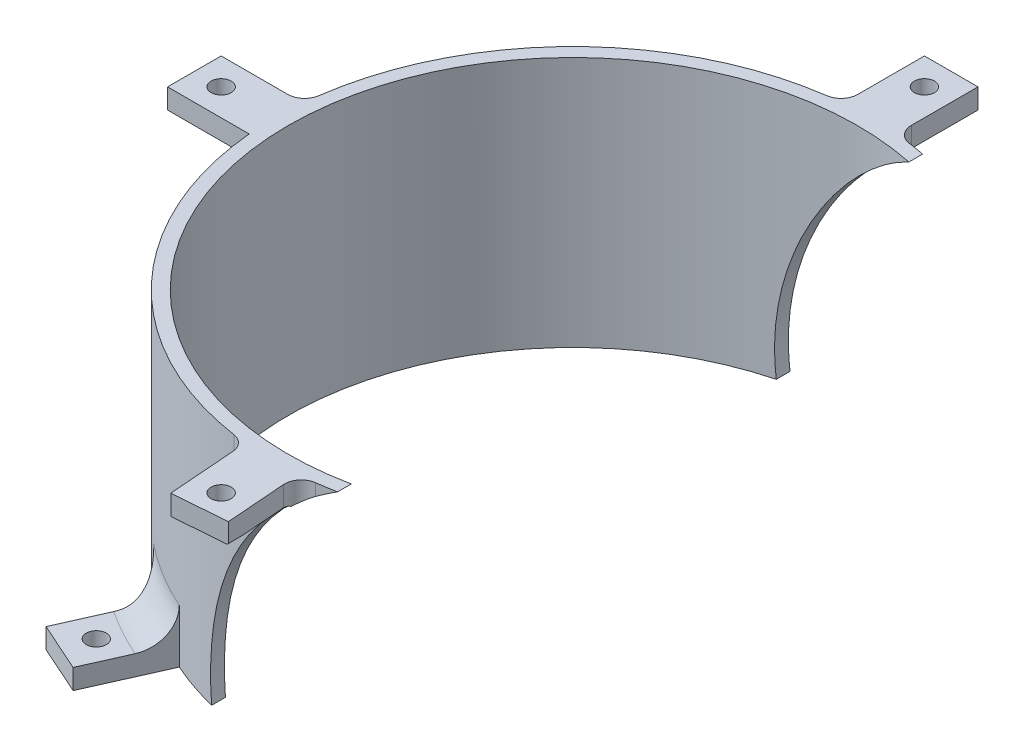
SolidWorks part; units mm, degrees
ref_plane "Front Plane" through (0, 0, 0) normal (0, 0, 1) x (1, 0, 0)
ref_plane "Top Plane" through (0, 0, 0) normal (0, 1, 0) x (1, 0, 0)
ref_plane "Right Plane" through (0, 0, 0) normal (1, 0, 0) x (0, 0, -1)
sketch "Sketch1" plane through (0, 0, 0) normal (0, 1, 0) x (1, 0, 0)
  circle A0 centre (0, 0) radius 85
  circle A1 centre (0, 0) radius 89
  arc A2 (-85, 0) -> (85, 0) centre (0, 0) cw construction
  arc A3 (-89, 0) -> (89, 0) centre (0, 0) cw construction
  dimension "D1" = 85
  dimension "D2" = 4
extrude "Boss-Extrude1" add sketch "Sketch1" along normal blind 75
sketch "Sketch2" plane through (0, 75, 0) normal (0, 1, 0) x (1, 0, 0)
  line L0 (8, 88.6397) -> (8, 113)
  line L1 (8, 113) -> (-8, 113)
  line L2 (-8, 113) -> (-8, 88.6397)
  line L3 (0, 0) -> (0, 105) construction
  line L4 (-113, 8) -> (-88.6397, 8)
  line L5 (-113, 8) -> (-113, -8)
  line L6 (-113, -8) -> (-88.6397, -8)
  line L17 (-88.6397, -8) -> (-85.6239, -8)
  line L18 (-85.6239, -8) -> (-85.6239, 8)
  line L19 (-85.6239, 8) -> (-88.6397, 8)
  line L20 (8, 88.6397) -> (8, 86.3334)
  line L21 (8, 86.3334) -> (-8, 86.3334)
  line L22 (-8, 86.3334) -> (-8, 88.6397)
  line L23 (6.6683, -87.267) -> (8.5101, -111.3701)
  line L24 (8.5101, -111.3701) -> (-7.4434, -112.5892)
  line L25 (-7.4434, -112.5892) -> (-9.3783, -87.267)
  line L26 (-9.3783, -87.267) -> (6.6683, -87.267)
  circle A1 centre (0, 0) radius 105 construction
  circle A2 centre (0, 105) radius 3
  circle A3 centre (-105, 0) radius 3
  circle A5 centre (0, 0) radius 89 construction
  circle A6 centre (0, -105) radius 3
  circle A7 centre (0, 0) radius 89 construction
  circle M3 centre (0, 0) radius 89
  dimension "D1" = 210
  dimension "D2" = 6
  dimension "D3" = 6
  dimension "D14" = 6
  dimension "D5" = 8
  dimension "D6" = 8
  dimension "D7" = 8
  dimension "D8" = 8
  dimension "D9" = 8
  dimension "D10" = 8
  dimension "D15" = 8
  dimension "D16" = 8
  dimension "D17" = 7
extrude "Boss-Extrude2" add sketch "Sketch2" against normal blind 6 contours M3 | L1 L2 L0 A2 M3 | L4 L5 L6 A3 M3 | L25 L24 L23 A6 M3 region at (0, 75, -100.6188) region at (-0.4687, 75, 100.05) region at (-100.6188, 75, 0)
fillet "Fillet1" radius 5 8 edges at (-89, 69, 0) (-88.6397, 72, -8) (0, 69, -89) (-1.2562, 69, 88.9911) (-8, 72, -88.6397) (8, 72, -88.6397) (6.781, 72, 88.7413) (-9.283, 72, 88.5146)
sketch "Sketch3" plane through (0, 0, 0) normal (0, -1, 0) x (1, 0, 0)
  line L0 (-113, 8) -> (-93.659, 8) construction
  line L1 (-113, -8) -> (-93.659, -8) construction
  line L2 (-113, -8) -> (-113, 8) construction
  line L3 (-113, 8) -> (-88.6397, 8)
  line L4 (-113, -8) -> (-88.6397, -8)
  line L5 (-113, -8) -> (-113, 8)
  line L6 (-88.6397, -8) -> (-86.5768, -8)
  line L7 (-86.5768, -8) -> (-86.5768, 8)
  line L8 (-86.5768, 8) -> (-88.6397, 8)
  line L9 (-45.9612, -103.2306) -> (-35.1057, -78.8488)
  line L10 (-45.9612, -103.2306) -> (-60.578, -96.7229)
  line L11 (-60.578, -96.7229) -> (-49.4614, -71.7547)
  line L12 (-49.4614, -71.7547) -> (-35.1057, -78.8488)
  line L13 (-35.5287, 79.7987) -> (-45.9612, 103.2306)
  line L14 (-45.9612, 103.2306) -> (-60.578, 96.7229)
  line L15 (-60.578, 96.7229) -> (-48.9386, 70.5803)
  line L16 (-48.9386, 70.5803) -> (-35.5287, 79.7987)
  circle A0 centre (0, 0) radius 89 construction
  point P17 (-86.5768, 0)
  dimension "D1" = 16
  dimension "D2" = 113
  dimension "D3" = 66
  dimension "D4" = 113
  dimension "D5" = 16
  dimension "D6" = 132
extrude "Boss-Extrude3" add sketch "Sketch3" against normal blind 6
fillet "Fillet2" radius 10 7 edges at (-88.6397, 3, -8) (-88.6397, 3, 8) (-89, 6, 0) (-43.3901, 6, -77.7065) (-50.2265, 3, -73.4731) (-43.3901, 6, 77.7065) (-50.2265, 3, 73.4731)
sketch "Sketch4" plane through (0, 6, 0) normal (0, 1, 0) x (1, 0, 0)
  line L0 (-53.2696, -99.9767) -> (-45.6622, -82.8901) construction
  line L1 (-45.9612, -103.2306) -> (-60.578, -96.7229) construction
  line L2 (-53.2696, 99.9767) -> (-42.9827, 76.8721) construction
  line L3 (-60.578, 96.7229) -> (-45.9612, 103.2306) construction
  circle A0 centre (-105, 0) radius 3 construction
  circle A1 centre (-105, 0) radius 3
  circle A2 centre (-49.8916, -92.3896) radius 3
  circle A3 centre (-49.8916, 92.3896) radius 3
  point P11 (0, 0)
  dimension "D1" = 6
  dimension "D2" = 6
  dimension "D3" = 105
  dimension "D4" = 105
extrude "Cut-Extrude1" cut sketch "Sketch4" against normal through all
sketch "Sketch5" plane through (0, 0, 0) normal (0, 0, 1) x (1, 0, 0)
  line L0 (89, 0) -> (89, 75) construction
  line L1 (89, 77.4697) -> (165.9577, -10.5357)
  line L2 (165.9577, -10.5357) -> (27.4359, -65.8768)
  line L3 (27.4359, -65.8768) -> (-25.1983, -65.8768)
  line L4 (-25.1983, -65.8768) -> (-21.4886, 0)
  arc A0 (89, 77.4697) -> (-21.4886, 0) centre (55.4082, 7.8538) ccw
extrude "Cut-Extrude2" cut sketch "Sketch5" against normal through all and the other way through all
